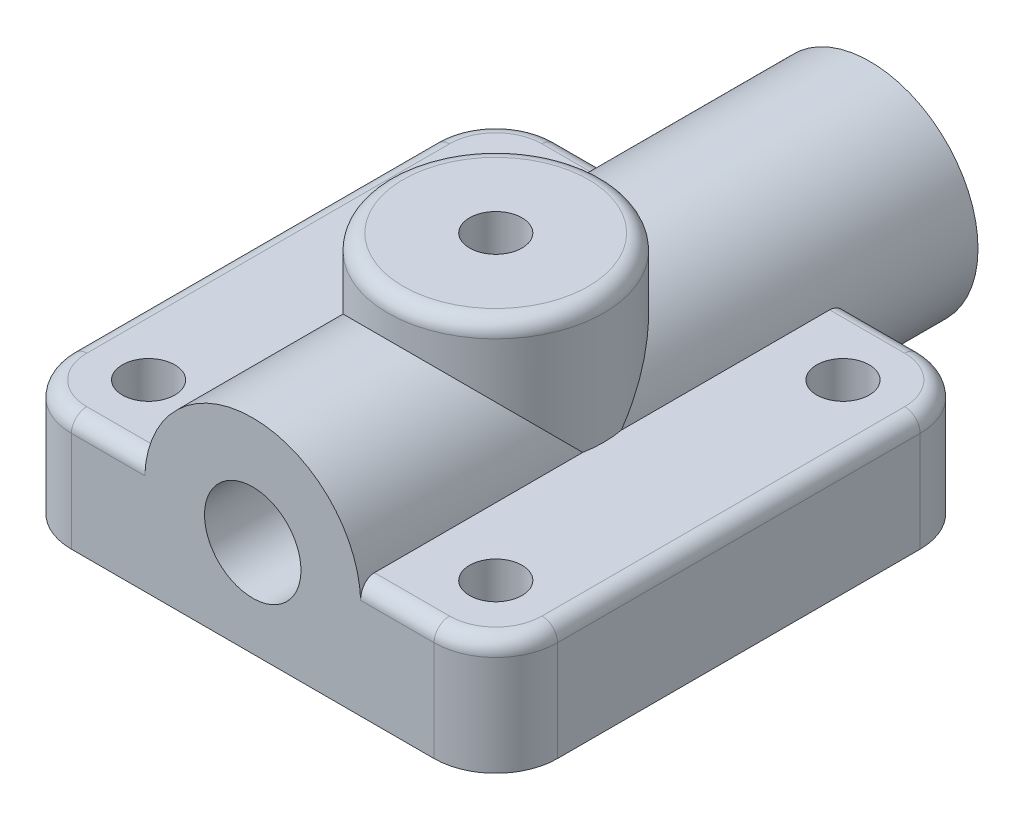
SolidWorks part; units mm, degrees
ref_plane "前视基准面" through (0, 0, 0) normal (0, 0, 1) x (1, 0, 0)
ref_plane "上视基准面" through (0, 0, 0) normal (0, 1, 0) x (1, 0, 0)
ref_plane "右视基准面" through (0, 0, 0) normal (1, 0, 0) x (0, 0, -1)
sketch "草图1" plane through (0, 0, 0) normal (0, 1, 0) x (1, 0, 0)
  line L1 (-23.5, 31.5) -> (23.5, 31.5)
  line L2 (-31.5, 23.5) -> (-31.5, -23.5)
  line L3 (-23.5, -31.5) -> (23.5, -31.5)
  line L4 (31.5, 23.5) -> (31.5, -23.5)
  line L5 (-31.5, 31.5) -> (31.5, -31.5) construction
  line L6 (-31.5, -31.5) -> (31.5, 31.5) construction
  arc A0 (-23.5, -31.5) -> (-31.5, -23.5) centre (-23.5, -23.5) cw
  arc A1 (23.5, -31.5) -> (31.5, -23.5) centre (23.5, -23.5) ccw
  arc A2 (31.5, 23.5) -> (23.5, 31.5) centre (23.5, 23.5) ccw
  arc A3 (-23.5, 31.5) -> (-31.5, 23.5) centre (-23.5, 23.5) ccw
  point P0 (0, 0)
  dimension "D3" = 8
  dimension "D1" = 63
  dimension "D2" = 63
extrude "凸台-拉伸1" add sketch "草图1" along normal blind 15
sketch "草图2" plane through (0, 15, 0) normal (0, 1, 0) x (1, 0, 0)
  circle A0 centre (0, 0) radius 14
  dimension "D1" = 28
extrude "凸台-拉伸2" add sketch "草图2" along normal blind 16.5
fillet "圆角1" radius 2 9 edges at (0, 15, -31.5) (31.5, 15, 0) (-31.5, 15, 0) (0, 15, 31.5) (29.1569, 15, 29.1569) (-29.1569, 15, 29.1569) (-29.1569, 15, -29.1569) (29.1569, 15, -29.1569) (0, 31.5, 14)
sketch "草图3" plane through (0, 0, -31.5) normal (0, 0, -1) x (-1, 0, 0)
  line L0 (-23.5, 0) -> (23.5, 0) construction
  line L5 (23.5, 0) -> (23.5, 13)
  line L6 (23.5, 13) -> (-23.5, 13)
  line L7 (-23.5, 13) -> (-23.5, 0)
  line L8 (-23.5, 0) -> (23.5, 0)
  line L12 (-6.3048, 0) -> (6.3048, 0)
  arc A0 (6.3048, 0) -> (-6.3048, 0) centre (0, 12.5) ccw
  dimension "D1" = 28
  dimension "D2" = 12.5
  dimension "D3" = 0
extrude "凸台-拉伸3" add sketch "草图3" along normal blind 17
sketch "草图4" plane through (0, 0, -31.5) normal (0, 0, 1) x (1, 0, 0)
  line L1 (-13.9911, 13) -> (13.9911, 13)
  line L2 (-13.9911, 13) -> (13.9911, 13)
  arc A1 (13.9911, 13) -> (-13.9911, 13) centre (0, 12.5) ccw
  arc A2 (13.9911, 13) -> (-13.9911, 13) centre (0, 12.5) ccw
  dimension "D1" = 0
extrude "凸台-拉伸4" add sketch "草图4" along normal blind 63
hole_wizard "M14x1.5 螺纹孔1" positions "草图5" profile "草图6" tap size "M14x1.5" standard "GB" end condition through all
sketch "草图5" plane through (0, 0, -48.5) normal (0, 0, -1) x (-1, 0, 0)
  point P0 (0, 12.5)
sketch "草图6" plane through (0, 12.5, -48.5) normal (1, 0, 0) x (0, 1, 0)
  line L0 (0, 0) -> (0, 80)
  line L1 (0, 80) -> (6.25, 80)
  line L2 (6.25, 80) -> (6.25, 0)
  line L5 (6.25, 0) -> (0, 0)
  line L11 (0, -6.35) -> (0, 107.95) construction
  dimension "通孔螺纹孔钻头直径" = 12.5
  dimension "通孔螺纹孔钻头深度" = 80
cosmetic thread "孔螺蚊线1" parameters "D2"=14
hole_wizard "M8 螺纹孔1" positions "草图7" profile "草图8" tap size "M8" standard "GB" end condition up to next
sketch "草图7" plane through (0, 31.5, 0) normal (0, 1, 0) x (1, 0, 0)
  point P0 (0, 0)
sketch "草图8" plane through (0, 31.5, 0) normal (1, 0, 0) x (0, 0, 1)
  line L0 (0, 0) -> (0, 12.75)
  line L1 (0, 12.75) -> (3.4, 12.75)
  line L2 (3.4, 12.75) -> (3.4, 0)
  line L5 (3.4, 0) -> (0, 0)
  line L11 (0, -6.35) -> (0, 107.95) construction
  dimension "通孔螺纹孔钻头直径" = 6.8
  dimension "通孔螺纹孔钻头深度" = 12.75
cosmetic thread "孔螺蚊线2" parameters "D2"=8
sketch "草图9" plane through (0, 0, 0) normal (0, -1, 0) x (1, 0, 0)
  line L0 (-14, -48.5) -> (14, -48.5) construction
  circle A0 centre (0, -15.5) radius 4.5
  dimension "D1" = 9
  dimension "D2" = 33
extrude "切除-拉伸1" cut sketch "草图9" against normal up to next
hole_wizard "M8 螺纹孔2" positions "草图10" profile "草图11" tap size "M8" standard "GB" end condition up to next
sketch "草图10" plane through (0, 15, 0) normal (0, 1, 0) x (1, 0, 0)
  line L0 (-23.5, 31.5) -> (-13.9911, 31.5) construction
  line L1 (-31.5, -23.5) -> (-31.5, 23.5) construction
  point P0 (-22.5, 22.5)
  dimension "D1" = 9
  dimension "D2" = 9
sketch "草图11" plane through (-22.5, 15, -22.5) normal (1, 0, 0) x (0, 0, 1)
  line L0 (0, 0) -> (0, 15)
  line L1 (0, 15) -> (3.4, 15)
  line L2 (3.4, 15) -> (3.4, 0)
  line L5 (3.4, 0) -> (0, 0)
  line L11 (0, -6.35) -> (0, 107.95) construction
  dimension "通孔螺纹孔钻头直径" = 6.8
  dimension "通孔螺纹孔钻头深度" = 15
cosmetic thread "孔螺蚊线3" parameters "D2"=8
ref_axis "基准轴1" through (0, 33.075, 0) along (0, -1, 0)
pattern_circular "阵列(圆周)1" count 4 over 360 about axis through (0, 33.075, 0) along (0, -1, 0) of "M8 螺纹孔2"
cosmetic thread "孔螺蚊线4" parameters "D2"=8
cosmetic thread "孔螺蚊线5" parameters "D2"=8
cosmetic thread "孔螺蚊线6" parameters "D2"=8
